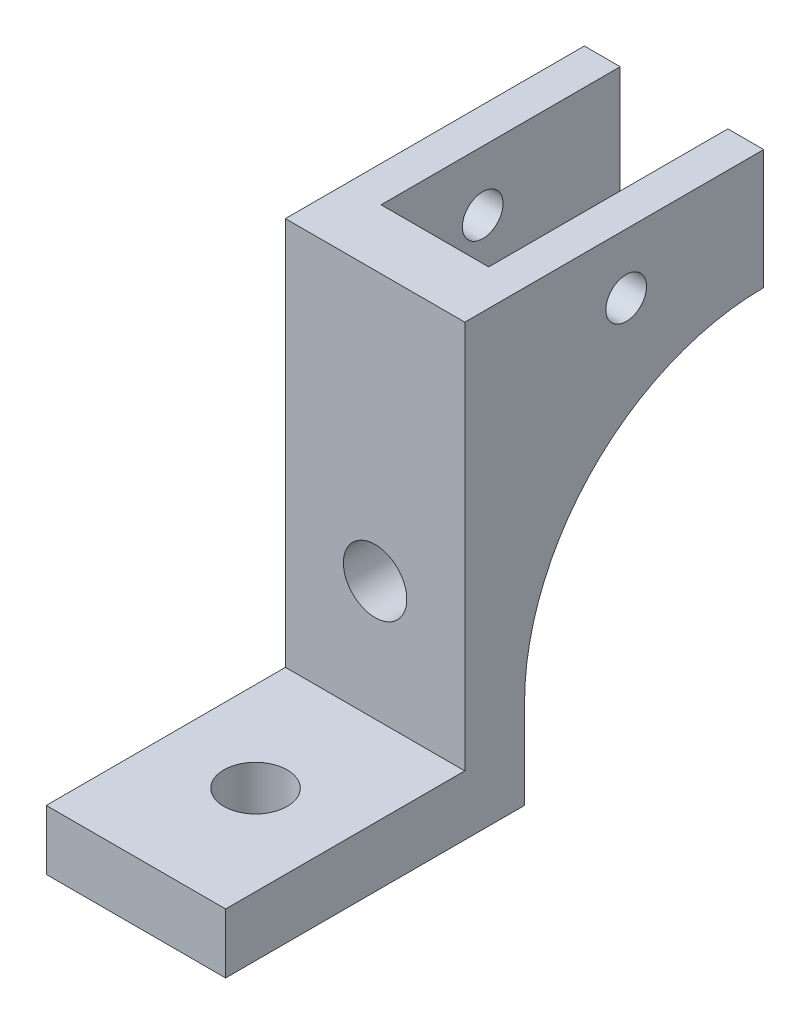
SolidWorks part; units mm, degrees
ref_plane "Front Plane" through (0, 0, 0) normal (0, 0, 1) x (1, 0, 0)
ref_plane "Top Plane" through (0, 0, 0) normal (0, 1, 0) x (1, 0, 0)
ref_plane "Right Plane" through (0, 0, 0) normal (1, 0, 0) x (0, 0, -1)
sketch "Sketch2" plane through (0, 0, 0) normal (0, 0, 1) x (1, 0, 0)
  line L1 (0, 0) -> (15, 0)
  line L2 (0, 0) -> (0, 37.5)
  line L3 (0, 37.5) -> (15, 37.5)
  line L4 (15, 0) -> (15, 37.5)
  dimension "D1" = 37.5
  dimension "D2" = 15
extrude "Boss-Extrude1" add sketch "Sketch2" along normal blind 5
sketch "Sketch3" plane through (0, 0, 5) normal (0, 0, 1) x (1, 0, 0)
  line L0 (15, 0) -> (15, 37.5) construction
  line L1 (0, 0) -> (15, 0)
  line L2 (0, 0) -> (0, 5)
  line L3 (0, 5) -> (15, 5)
  line L4 (15, 0) -> (15, 5)
  dimension "D1" = 5
extrude "Boss-Extrude2" add sketch "Sketch3" along normal blind 20
sketch "Sketch4" plane through (0, 0, 0) normal (0, 0, -1) x (-1, 0, 0)
  line L1 (-15, 37.5) -> (-12, 37.5)
  line L2 (-15, 37.5) -> (-15, 27.5)
  line L3 (-15, 27.5) -> (-12, 27.5)
  line L4 (-12, 37.5) -> (-12, 27.5)
  line L5 (0, 37.5) -> (-3, 37.5)
  line L6 (0, 37.5) -> (0, 27.5)
  line L7 (0, 27.5) -> (-3, 27.5)
  line L8 (-3, 37.5) -> (-3, 27.5)
  dimension "D1" = 3
  dimension "D2" = 3
  dimension "D3" = 10
  dimension "D4" = 10
extrude "Boss-Extrude3" add sketch "Sketch4" along normal blind 20
sketch "Sketch5" plane through (15, 0, 0) normal (1, 0, 0) x (0, 0, -1)
  circle A0 centre (8.5, 32.5) radius 1.7
  dimension "D1" = 3.4
extrude "Cut-Extrude1" cut sketch "Sketch5" against normal through all both and the other way through all
fillet "Fillet1" radius 20 2 edges at (1.5, 27.5, 0) (13.5, 27.5, 0)
sketch "Sketch6" plane through (0, 0, 0) normal (0, -1, 0) x (1, 0, 0)
  line L0 (0, 25) -> (15, 25) construction
  line L1 (0, 25) -> (0, 0) construction
  circle A0 centre (7.5, 15) radius 2.65
  point P6 (0, 0)
  dimension "D1" = 5.3
  dimension "D2" = 10
  dimension "D3" = 7.5
extrude "Cut-Extrude2" cut sketch "Sketch6" against normal blind 10
sketch "Sketch7" plane through (0, 0, 0) normal (0, 0, -1) x (-1, 0, 0)
  line L0 (0, 0) -> (-15, 0) construction
  line L1 (0, 7.5) -> (0, 0) construction
  circle A0 centre (-7.5, 15) radius 2.65
  dimension "D1" = 5.3
  dimension "D2" = 15
  dimension "D3" = 7.5
extrude "Cut-Extrude3" cut sketch "Sketch7" against normal blind 10
